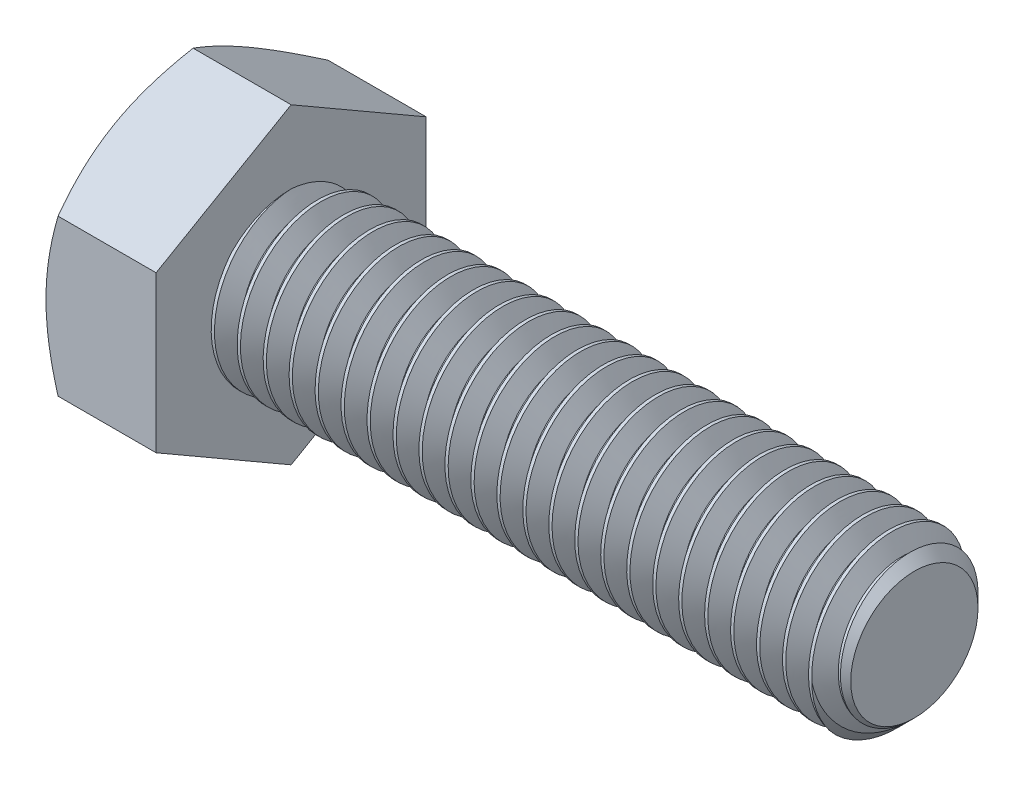
SolidWorks part; units mm, degrees
ref_plane "Front Plane" through (0, 0, 0) normal (0, 0, 1) x (1, 0, 0)
ref_plane "Top Plane" through (0, 0, 0) normal (0, 1, 0) x (1, 0, 0)
ref_plane "Right Plane" through (0, 0, 0) normal (1, 0, 0) x (0, 0, -1)
sketch "Sketch1" plane through (0, 0, 0) normal (0, 0, 1) x (1, 0, 0)
  line L0 (-17.65, 0) -> (17.65, 0) construction
  line L1 (-12.35, 6.5) -> (-12.35, -6.5) construction
  line L2 (-17.65, 6.5) -> (-17.65, -6.5) construction
  line L3 (17.65, 4) -> (17.65, -4) construction
  point P8 (13.275, -4)
  dimension "Thread Dia" = 8
  dimension "Hex" = 13
  dimension "Head Ht" = 5.3
  dimension "Length" = 30
  dimension "D1" = 4.375
ref_plane "Plane2" through (17.65, 0, 0) normal (1, 0, 0) x (0, 0, -1)
sketch "Sketch2" plane through (17.65, 0, 0) normal (1, 0, 0) x (0, 0, -1)
  circle A0 centre (0, 0) radius 4
extrude "Boss-Extrude1" add sketch "Sketch2" against normal up to vertex (30 mm away) up to point (-12.35, -6.5, 0)
sketch "Sketch4" plane through (17.65, 0, 0) normal (1, 0, 0) x (0, 0, -1)
  circle A1 centre (0, 0) radius 4
  circle A2 centre (0, 0) radius 4
  dimension "D1" = 0
curve "Helix/Spiral1" pitch 1.25 height 31.25 turns 25 parameters "Pitch"=1.25
chamfer "Chamfer1" distance 0.9375 angle 45 1 edges at (17.65, 0, -4)
sketch "Sketch5" plane through (0, 0, 0) normal (0, 0, 1) x (1, 0, 0)
  line L0 (17.65, 4) -> (18.1187, 3.1881)
  line L1 (18.1187, 3.1881) -> (18.275, 3.1881)
  line L2 (18.275, 3.1881) -> (18.7437, 4)
  line L3 (17.65, 4) -> (18.7437, 4)
  line L4 (18.1969, 3.1881) -> (18.1969, 4) construction
  line L5 (17.8844, 3.5941) -> (18.5094, 3.5941) construction
  line L6 (17.65, -4) -> (17.65, 4) construction
  dimension "D1" = 60
  dimension "D2" = 0.1562
  dimension "D3" = 0.625
sweep "Cut-Sweep1" cut profiles "Sketch5" path "Helix/Spiral1"
sketch "Sketch3" plane through (-12.35, 0, 0) normal (-1, 0, 0) x (0, 0, 1)
  line L0 (0, 6.5) -> (0, -6.5) construction
  line L1 (-6.5, -3.7528) -> (0, -7.5056)
  line L2 (0, -7.5056) -> (6.5, -3.7528)
  line L3 (6.5, -3.7528) -> (6.5, 3.7528)
  line L4 (6.5, 3.7528) -> (0, 7.5056)
  line L5 (0, 7.5056) -> (-6.5, 3.7528)
  line L6 (-6.5, 3.7528) -> (-6.5, -3.7528)
  circle A0 centre (0, 0) radius 6.5 construction
extrude "Boss-Extrude2" add sketch "Sketch3" along normal up to vertex (5.3 mm away) up to point (-17.65, -6.5, 0)
sketch "Sketch6" plane through (-17.65, 0, 0) normal (-1, 0, 0) x (0, 0, 1)
  circle A0 centre (0, 0) radius 6.5 construction
  circle A1 centre (0, 0) radius 6.5
extrude "Cut-Extrude1" cut sketch "Sketch6" against normal through all draft 60 flip side to cut
sketch "Sketch7" plane through (-17.65, 0, 0) normal (-1, 0, 0) x (0, 0, 1)
  line L0 (0, 0) -> (0, 6.5) construction
  line L2 (0, 6.5) -> (0, -6.5) construction
  line L3 (-5.6292, 3.25) -> (5.6292, 3.25) construction
  circle A1 centre (0, 0) radius 6.5 construction
  text T0 "10.9" font "Arial" height in points 8
  point P8 (0, 3.25)
extrude "Cut-Extrude2" cut sketch "Sketch7" against normal blind 0.25
sketch "Sketch9" plane through (0, 0, 0) normal (0, 0, 1) x (1, 0, 0)
  line L0 (-12.35, 4) -> (-12.35, 0)
  line L1 (-12.35, 0) -> (3.65, 0)
  line L2 (3.65, 0) -> (-0.35, 4)
  line L3 (-0.35, 4) -> (-12.35, 4)
  line L4 (-17.65, 0) -> (17.65, 0) construction
  line L5 (-12.35, 6.5) -> (-12.35, -6.5) construction
  line L6 (17.65, 4) -> (17.65, -4) construction
  dimension "D1" = 45
  dimension "MinThreadLg" = 18
revolve "Revolve1" [suppressed] add sketch "Sketch9" angle 360 about L1
equation "\"D2@Sketch5\" = \"Pitch@Helix/Spiral1\"*.125"
equation "\"D3@Sketch5\" = \"Pitch@Helix/Spiral1\"*.50"
equation "\"D3@Helix/Spiral1\" = \"Length@Sketch1\"+\"Pitch@Helix/Spiral1\""
equation "\"D1@Chamfer1\" = \"Pitch@Helix/Spiral1\"*.750"
equation "\"D1@Sketch1\" = \"Pitch@Helix/Spiral1\"*3.50"
